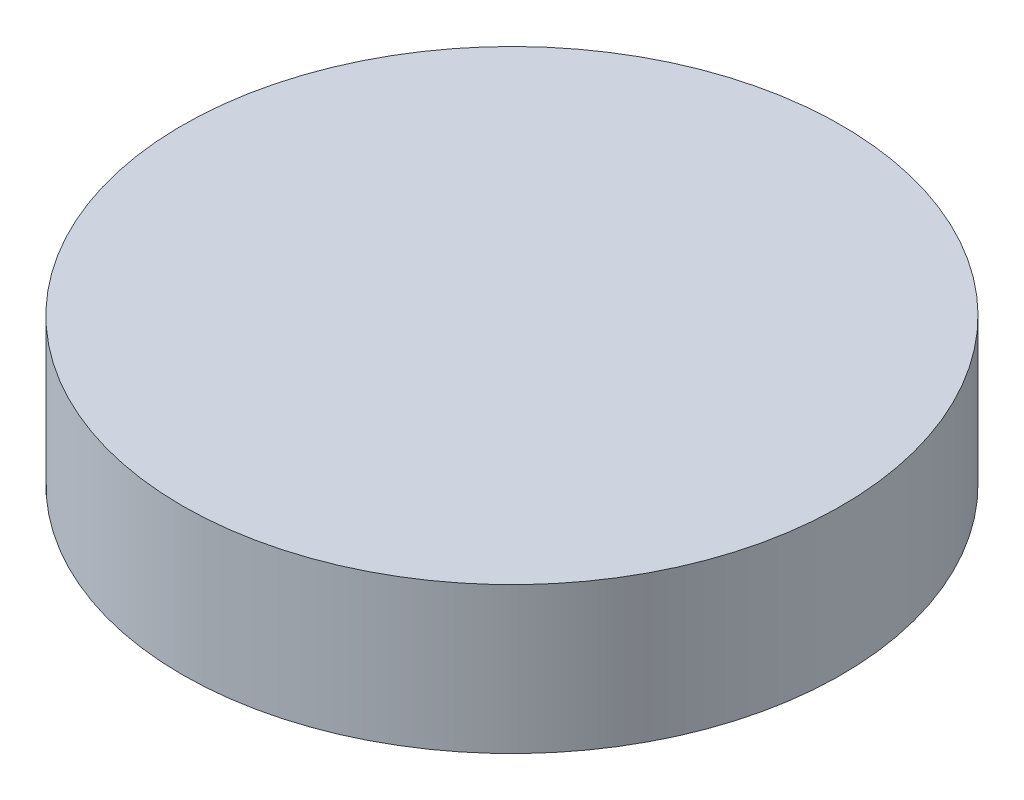
SolidWorks part; units mm, degrees
ref_plane "Front Plane" through (0, 0, 0) normal (0, 0, 1) x (1, 0, 0)
ref_plane "Top Plane" through (0, 0, 0) normal (0, 1, 0) x (1, 0, 0)
ref_plane "Right Plane" through (0, 0, 0) normal (1, 0, 0) x (0, 0, -1)
sketch "Sketch1" plane through (0, 0, 0) normal (0, 1, 0) x (1, 0, 0)
  circle A0 centre (0, 0) radius 18.375
  dimension "D1" = 36.75
extrude "Boss-Extrude1" add sketch "Sketch1" along normal blind 8.1569
